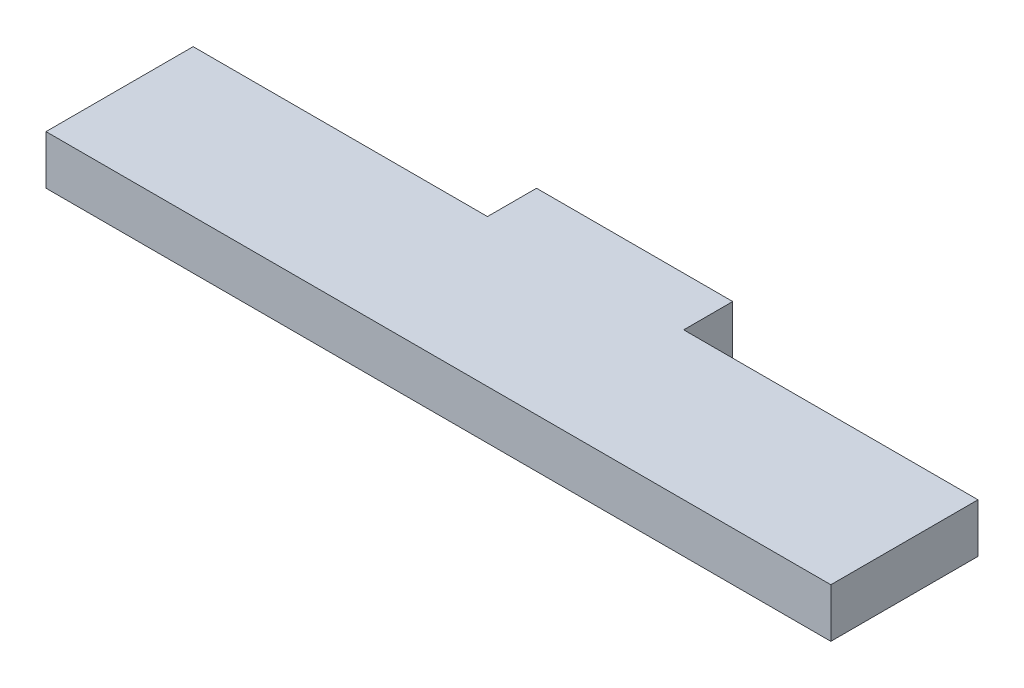
SolidWorks part; units mm, degrees
ref_plane "Front Plane" through (0, 0, 0) normal (0, 0, 1) x (1, 0, 0)
ref_plane "Top Plane" through (0, 0, 0) normal (0, 1, 0) x (1, 0, 0)
ref_plane "Right Plane" through (0, 0, 0) normal (1, 0, 0) x (0, 0, -1)
sketch "Sketch1" plane through (0, 0, 0) normal (0, 1, 0) x (1, 0, 0)
  line L1 (-21.1425, 19.05) -> (80.4575, 19.05)
  line L2 (-21.1425, 19.05) -> (-21.1425, -6.35)
  line L3 (-21.1425, -6.35) -> (80.4575, -6.35)
  line L4 (80.4575, 19.05) -> (80.4575, -6.35)
  dimension "D1" = 25.4
  dimension "D2" = 101.6
extrude "Boss-Extrude1" add sketch "Sketch1" along normal blind 6.35
sketch "Sketch2" plane through (0, 6.35, 0) normal (0, 1, 0) x (1, 0, 0)
  line L0 (80.4575, 19.05) -> (-21.1425, 19.05) construction
  line L1 (-21.1425, 19.05) -> (16.9575, 19.05)
  line L2 (-21.1425, 19.05) -> (-21.1425, 12.7)
  line L3 (-21.1425, 12.7) -> (16.9575, 12.7)
  line L4 (16.9575, 19.05) -> (16.9575, 12.7)
  line L5 (-21.1425, 19.05) -> (-21.1425, -6.35) construction
  line L6 (80.4575, -6.35) -> (80.4575, 19.05) construction
  line L7 (42.3575, 19.05) -> (80.4575, 19.05)
  line L8 (42.3575, 19.05) -> (42.3575, 12.7)
  line L9 (42.3575, 12.7) -> (80.4575, 12.7)
  line L10 (80.4575, 19.05) -> (80.4575, 12.7)
  point P12 (80.4575, 15.875)
  dimension "D1" = 38.1
  dimension "D2" = 6.35
  dimension "D3" = 6.35
  dimension "D4" = 38.1
extrude "Cut-Extrude1" cut sketch "Sketch2" against normal through all both and the other way through all
